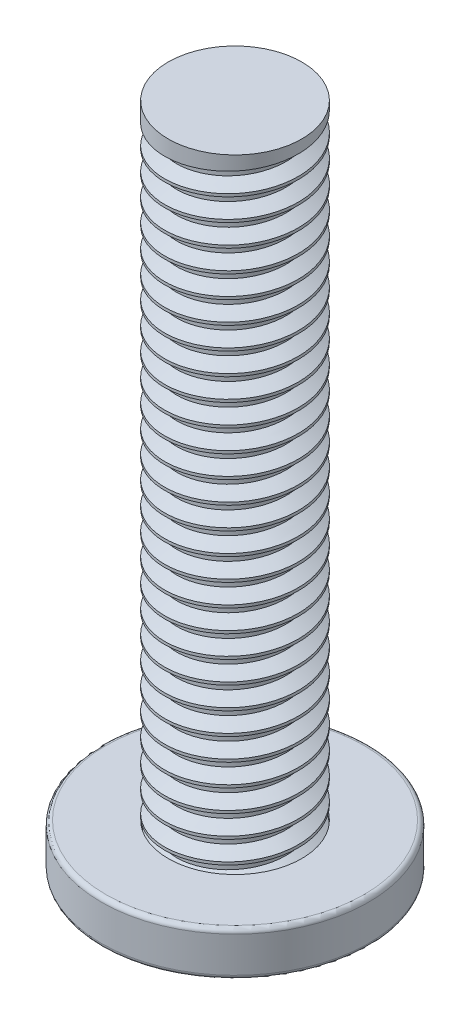
SolidWorks part; units mm, degrees
ref_plane "Front Plane" through (0, 0, 0) normal (0, 0, 1) x (1, 0, 0)
ref_plane "Top Plane" through (0, 0, 0) normal (0, 1, 0) x (1, 0, 0)
ref_plane "Right Plane" through (0, 0, 0) normal (1, 0, 0) x (0, 0, -1)
sketch "Sketch2" plane through (0, 0, 0) normal (0, 1, 0) x (1, 0, 0)
  circle A0 centre (0, 0) radius 3
  dimension "D1" = 6
extrude "Boss-Extrude1" add sketch "Sketch2" along normal blind 1
sketch "Sketch3" plane through (0, 1, 0) normal (0, 1, 0) x (1, 0, 0)
  circle A0 centre (0, 0) radius 1.5
  dimension "D1" = 3
extrude "Boss-Extrude2" add sketch "Sketch3" along normal blind 14
thread "Thread1" pitch 0.5 method cut profile "Thread Profile1" start angle 0, offset 0, length 0, pitch 0.5, diameter 3
ref_plane "Plane1" through (-1.5, 15, 0) normal (0, 0, 1) x (-1, 0, 0)
sketch "Thread Profile1" plane through (-1.5, 15, 0) normal (0, 0, 1) x (-1, 0, 0)
  line L0 (0, 0) -> (0, 0.5) construction
  line L11 (0, 0) -> (0, 0.4375)
  line L12 (0, 0.4375) -> (-0.2706, 0.2812)
  line L13 (-0.2706, 0.2812) -> (-0.2706, 0.1562)
  line L15 (-0.2706, 0.1562) -> (0, 0)
  line L17 (-0.2706, 0.2187) -> (0, 0.2187) construction
  point P2 (0, 0)
  dimension "Pitch" = 0.5
  dimension "Profile_Angle" = 60
  dimension "Profile_Land" = 0.125
  dimension "Profile_Height" = 0.2706
sketch "Sketch13" plane through (0, 0, 0) normal (0, -1, 0) x (1, 0, 0)
  line L1 (1.1547, 0) -> (0.5774, 1)
  line L2 (0.5774, 1) -> (-0.5774, 1)
  line L3 (-0.5774, 1) -> (-1.1547, 0)
  line L4 (-1.1547, 0) -> (-0.5774, -1)
  line L5 (-0.5774, -1) -> (0.5774, -1)
  line L6 (0.5774, -1) -> (1.1547, 0)
  circle A0 centre (0, 0) radius 1 construction
  circle A4 centre (0, 0) radius 3 construction
  dimension "D1" = 2
extrude "Cut-Extrude1" cut sketch "Sketch13" against normal blind 0.5
fillet "Fillet1" radius 0.1 2 edges at (0, 1, 3) (0, 0, 3)
